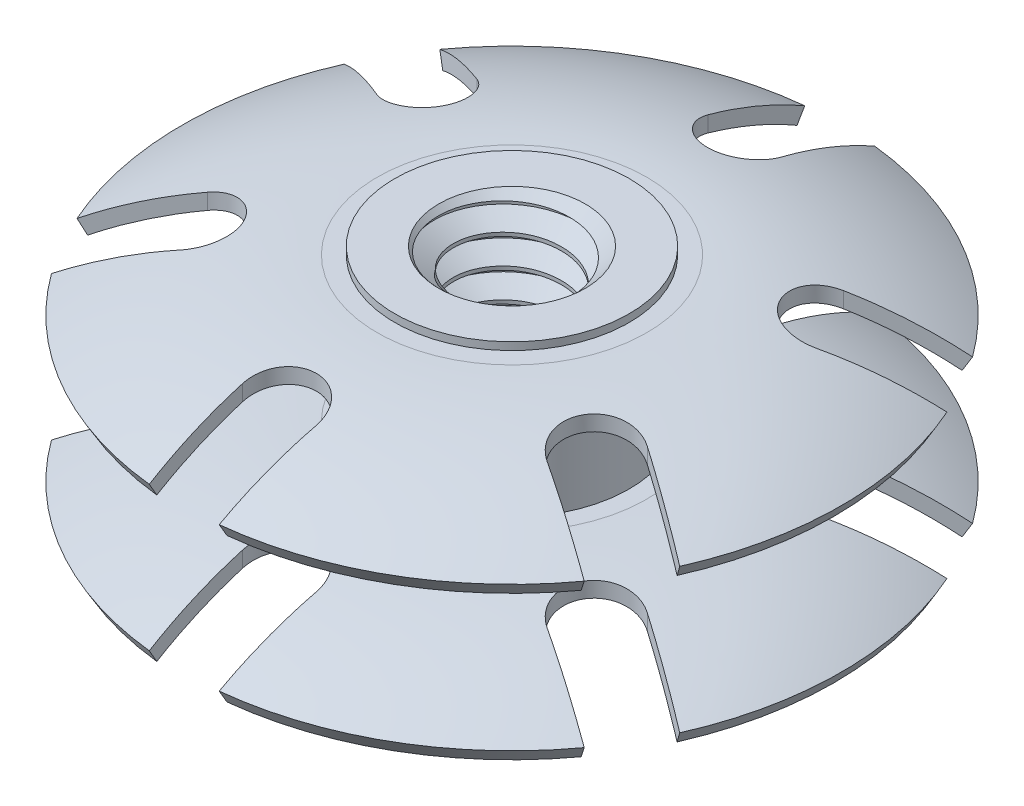
SolidWorks part; units mm, degrees
ref_plane "Front Plane" through (0, 0, 0) normal (0, 0, 1) x (1, 0, 0)
ref_plane "Top Plane" through (0, 0, 0) normal (0, 1, 0) x (1, 0, 0)
ref_plane "Right Plane" through (0, 0, 0) normal (1, 0, 0) x (0, 0, -1)
sketch "Sketch1" plane through (0, 0, 0) normal (0, 0, 1) x (1, 0, 0)
  line L0 (0, -2.794) -> (0, 2.794) construction
  line L1 (14.2875, 2.794) -> (-14.2875, 2.794) construction
  line L2 (3.175, 2.794) -> (-3.175, 2.794) construction
  line L3 (3.175, 2.794) -> (3.175, 1.524) construction
  point P4 (0, 0)
  point P8 (0, 2.794)
  point P11 (0, 2.794)
  dimension "Length" = 5.588
  dimension "For OD" = 28.575
  dimension "Thread Size" = 6.35
  dimension "Pitch" = 1.27
sketch "Sketch2" plane through (0, 0, 0) normal (0, 0, 1) x (1, 0, 0)
  line L0 (0, 0) -> (0, 3.7846) construction
  line L1 (-5.08, 3.7846) -> (-3.175, 3.7846)
  line L2 (-5.08, 3.7846) -> (-5.08, 3.4544)
  line L3 (-5.08, -3.7846) -> (-3.175, -3.7846)
  line L4 (-3.175, 3.7846) -> (-3.175, -3.7846)
  line L5 (0, 0) -> (-3.175, 0) construction
  line L6 (-5.08, -3.4544) -> (-5.08, -3.7846)
  line L7 (-5.08, 3.4544) -> (-4.572, 3.4544)
  line L9 (-5.08, 2.794) -> (-4.572, 2.794)
  line L10 (-4.572, 3.4544) -> (-4.572, 2.794)
  line L11 (-5.08, -2.794) -> (-4.572, -2.794)
  line L12 (-5.08, 2.794) -> (-5.08, -2.794)
  line L13 (-5.08, -3.4544) -> (-4.572, -3.4544)
  line L14 (-4.572, -2.794) -> (-4.572, -3.4544)
  dimension "ID" = 6.35
  dimension "D1" = 10.16
  dimension "D3" = 0.6604
  dimension "D5" = 9.144
  dimension "D2" = 5.588
  dimension "D4" = 0.3302
revolve "Revolve1" add sketch "Sketch2" angle 360 about L0
sketch "Sketch3" plane through (0, 3.7846, 0) normal (0, 1, 0) x (1, 0, 0)
  circle A0 centre (0, 0) radius 3.175 construction
  circle A1 centre (0, 0) radius 3.175
sketch "Sketch4" plane through (0, -3.7846, 0) normal (0, -1, 0) x (1, 0, 0)
  circle A1 centre (0, 0) radius 3.175
  circle A2 centre (0, 0) radius 3.175
  dimension "D1" = 0
sketch "Sketch5" plane through (0, 0, 0) normal (0, 0, 1) x (1, 0, 0)
  line L0 (-5.08, 2.794) -> (-4.572, 2.794) construction
  line L1 (-5.842, 3.4544) -> (-4.572, 3.4544)
  line L2 (-13.9573, 0.6195) -> (-14.2875, 1.1914)
  line L3 (-5.842, 2.794) -> (-4.572, 2.794)
  line L4 (-4.572, 3.4544) -> (-4.572, 2.794)
  line L5 (0, 0) -> (0, 3.7846) construction
  line L6 (-5.842, -2.794) -> (-4.572, -2.794)
  line L7 (-13.9573, -5.6289) -> (-14.2875, -5.057)
  line L8 (-5.842, -3.4544) -> (-4.572, -3.4544)
  line L9 (-4.572, -2.794) -> (-4.572, -3.4544)
  line L10 (-5.842, 3.4544) -> (-14.2875, 1.1914) construction
  arc A0 (-5.842, 2.794) -> (-13.9573, 0.6195) centre (-5.842, -13.4366) ccw
  arc A1 (-5.842, 3.4544) -> (-14.2875, 1.1914) centre (-5.842, -13.4366) ccw
  arc A2 (-5.842, -3.4544) -> (-13.9573, -5.6289) centre (-5.842, -19.685) ccw
  arc A3 (-5.842, -2.794) -> (-14.2875, -5.057) centre (-5.842, -19.685) ccw
  dimension "D1" = 11.684
  dimension "OD" = 28.575
  dimension "D2" = 195
revolve "Revolve2" add sketch "Sketch5" angle 360 about L5
sketch "Sketch6" plane through (0, 3.7846, 0) normal (0, 1, 0) x (1, 0, 0)
  line L0 (0, 5.842) -> (0, 14.2875) construction
  line L1 (-1.5873, 10.0925) -> (-1.5154, 14.2069)
  line L2 (1.5873, 10.0925) -> (1.5154, 14.2069)
  circle A0 centre (0, 0) radius 5.842 construction
  circle A1 centre (0, 0) radius 14.2875 construction
  arc A2 (-1.5873, 10.0925) -> (1.5873, 10.0925) centre (0, 10.0648) ccw
  arc A3 (1.5154, 14.2069) -> (-1.5154, 14.2069) centre (0, 0) ccw
  dimension "D1" = 1.5875
  dimension "D2" = 1
extrude "Cut-Extrude1" cut sketch "Sketch6" against normal through all
pattern_circular "CirPattern1" count 6 over 360 of "Cut-Extrude1"
sketch "Sketch7" plane through (0, 3.7846, 0) normal (0, 1, 0) x (1, 0, 0)
  line L0 (0, 0) -> (2.2451, 2.2451) construction
  line L1 (0, 0) -> (2.2451, -2.2451) construction
  line L2 (0, -4.9044) -> (0, 4.9044) construction
  circle A0 centre (0, 0) radius 14.2875
  circle A1 centre (0, 0) radius 3.175 construction
  point P11 (2.2451, -2.2451)
  point P12 (2.2451, 2.2451)
  dimension "D1" = 45
sketch "Sketch14" plane through (0, 0, 0) normal (0, 0, 1) x (1, 0, 0)
  line L0 (-5.08, -2.794) -> (-5.08, 2.794)
  line L1 (5.08, 2.794) -> (5.08, -2.794)
  line L2 (5.08, 2.794) -> (5.08, -2.794) construction
  line L3 (-5.08, -2.794) -> (-5.08, 2.794) construction
  point P5 (-5.08, 2.794)
  point P6 (5.08, 2.794)
  point P7 (-5.08, -2.794)
  point P8 (5.08, -2.794)
sketch "Sketch8" plane through (0, 3.7846, 0) normal (0, 1, 0) x (1, 0, 0)
  circle A0 centre (0, 0) radius 3.175 construction
  circle A1 centre (0, 0) radius 3.175
extrude "Boss-Extrude1" add sketch "Sketch8" against normal up to surface (7.5692 mm away) separate body up to face at (0, -3.7846, -3.175)
sketch "Sketch9" plane through (0, 3.7846, 0) normal (0, 1, 0) x (1, 0, 0)
  circle A0 centre (0, 0) radius 3.175 construction
  circle A1 centre (0, 0) radius 3.175
extrude "Boss-Extrude2" add sketch "Sketch9" against normal up to surface (7.5692 mm away) up to face at (0, -3.7846, -3.175)
sketch "Sketch10" plane through (0, 3.7846, 0) normal (0, 1, 0) x (1, 0, 0)
  circle A0 centre (0, 0) radius 3.175 construction
  circle A1 centre (0, 0) radius 3.175
curve "Helix/Spiral1" pitch 1.27 height 8.763 radius 3.175 centre (0, 3.7846, 0) axis (0, -1, 0) start towards (1, 0, 0)
sketch "Sketch11" plane through (0, 0, 0) normal (0, 0, 1) x (1, 0, 0)
  line L0 (3.175, 2.794) -> (3.175, 3.9053)
  line L1 (3.175, 3.9053) -> (2.3501, 3.429)
  line L2 (2.3501, 3.429) -> (2.3501, 3.2703)
  line L3 (2.3501, 3.2703) -> (3.175, 2.794)
  line L4 (2.3501, 3.3496) -> (3.175, 3.3496) construction
  line L5 (2.7626, 3.6671) -> (2.7626, 3.0321) construction
  dimension "D1" = 60
  dimension "D2" = 0.1588
  dimension "D3" = 0.635
sweep "Cut-Sweep1" cut profiles "Sketch11" path "Helix/Spiral1" align with end faces yes
combine bodies "Combine1" operation type subtract main body 115 bodies to subtract 116
sketch "Sketch12" plane through (0, 3.7846, 0) normal (0, 1, 0) x (1, 0, 0)
  circle A1 centre (0, 0) radius 3.175
  circle A2 centre (0, 0) radius 3.175
  dimension "D1" = 0
extrude "Cut-Extrude2" cut sketch "Sketch12" against normal through all draft 45
sketch "Sketch13" plane through (0, -3.7846, 0) normal (0, -1, 0) x (1, 0, 0)
  circle A1 centre (0, 0) radius 3.175
  circle A2 centre (0, 0) radius 3.175
  dimension "D1" = 0
extrude "Cut-Extrude3" cut sketch "Sketch13" against normal through all draft 45
equation "\"D1@Sketch2\" = \"ID@Sketch2\" * 1.6"
equation "\"D5@Sketch2\" = \"D1@Sketch2\" * .9"
equation "\"D3@Helix/Spiral1\" = \"D2@Sketch2\" + .125"
equation "\"D1@Sketch5\" = \"D1@Sketch2\" * 1.15"
equation "\"D1@Sketch6\" = \"OD@Sketch5\" / 18"
equation "\"ID@Sketch2\" = \"Thread Size@Sketch1\""
equation "\"OD@Sketch5\" = \"For OD@Sketch1\""
equation "\"pitch\"= \"Pitch@Sketch1\""
equation "\"D4@Helix/Spiral1\" = \"Pitch@Sketch1\""
equation "\"D2@Sketch11\" = \"Pitch@Sketch1\" * .125"
equation "\"D3@Sketch11\" = \"Pitch@Sketch1\" * .5"
equation "\"D2@Sketch2\"=\"Length@Sketch1\""
equation "\"D4@Sketch2\"=\"D3@Sketch2\"/2"
